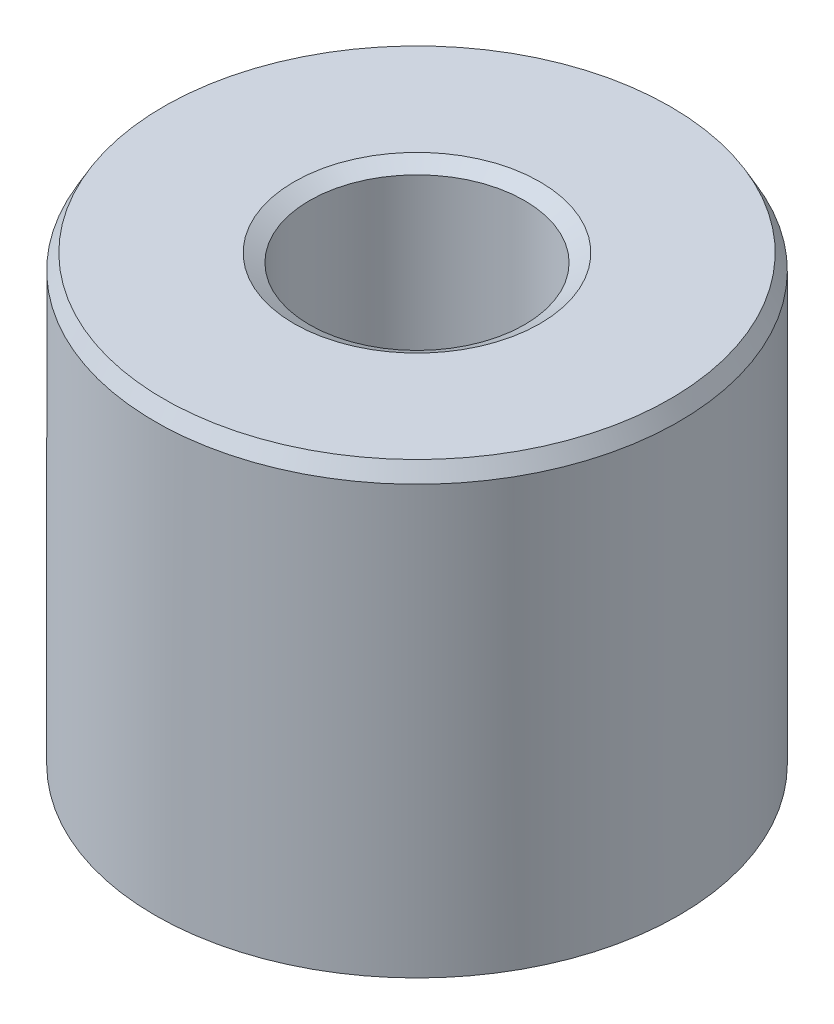
SolidWorks part; units mm, degrees
ref_plane "Front Plane" through (0, 0, 0) normal (0, 0, 1) x (1, 0, 0)
ref_plane "Top Plane" through (0, 0, 0) normal (0, 1, 0) x (1, 0, 0)
ref_plane "Right Plane" through (0, 0, 0) normal (1, 0, 0) x (0, 0, -1)
sketch "Sketch1" plane through (0, 0, 0) normal (0, 1, 0) x (1, 0, 0)
  circle A0 centre (0, 0) radius 7.5
  dimension "SLEEVE_OD" = 15
extrude "Boss-Extrude1" add sketch "Sketch1" along normal blind 12.9314
sketch "Sketch2" plane through (0, 0, 0) normal (0, 1, 0) x (1, 0, 0)
  circle A0 centre (0, 0) radius 3.0809
  dimension "BORE_D" = 6.1618
extrude "Cut-Extrude1" cut sketch "Sketch2" along normal through all
chamfer "Chamfer1" distance 0.4402 angle 29.177 4 edges at (0, 12.9314, 3.0809) (0, 0, 3.0809) (0, 0, 7.5) (0, 12.9314, 7.5) first distance on face at (0, 12.9314, 3.0809) first distance on face at (0, 0, 3.0809) first distance on face at (0, 12.9314, 7.5)
